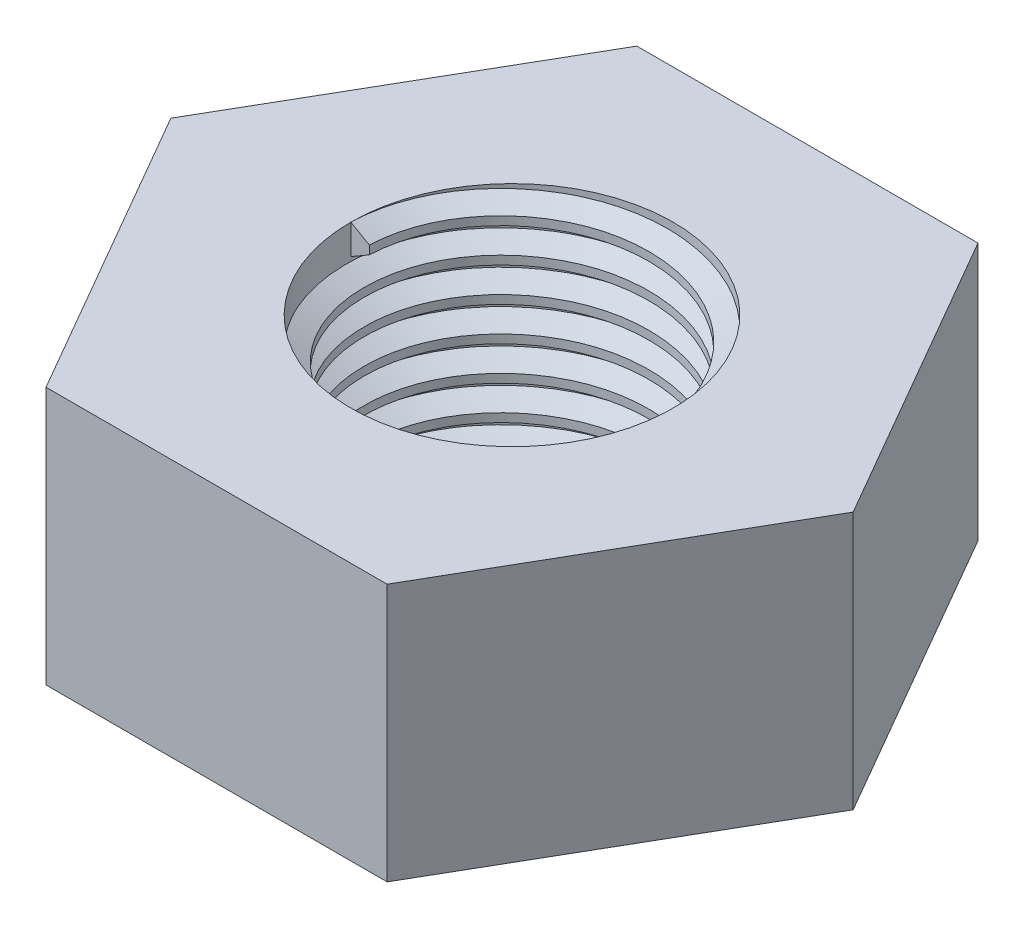
SolidWorks part; units mm, degrees
ref_plane "Ebene vorne" through (0, 0, 0) normal (0, 0, 1) x (1, 0, 0)
ref_plane "Ebene oben" through (0, 0, 0) normal (0, 1, 0) x (1, 0, 0)
ref_plane "Ebene rechts" through (0, 0, 0) normal (1, 0, 0) x (0, 0, -1)
sketch "Skizze2" plane through (0, 0, 0) normal (0, 1, 0) x (1, 0, 0)
  line L1 (3.1754, 0) -> (1.5877, 2.75)
  line L2 (1.5877, 2.75) -> (-1.5877, 2.75)
  line L3 (-1.5877, 2.75) -> (-3.1754, 0)
  line L4 (-3.1754, 0) -> (-1.5877, -2.75)
  line L5 (-1.5877, -2.75) -> (1.5877, -2.75)
  line L6 (1.5877, -2.75) -> (3.1754, 0)
  circle A0 centre (0, 0) radius 2.75 construction
  point P1 (0, 0)
  dimension "D1" = 5.5
extrude "Aufsatz-Linear austragen1" add sketch "Skizze2" along normal blind 2.4
sketch "Skizze3" plane through (0, 2.4, 0) normal (0, 1, 0) x (1, 0, 0)
  circle A0 centre (0, 0) radius 1.5
  dimension "D1" = 3
extrude "Schnitt-Linear austragen1" cut sketch "Skizze3" against normal up to surface (2.4 mm away) up to face at (0, 0, 0)
thread "Gewinde1" pitch 0.3175 method extrude profile "Gewindeprofil1" start angle 0, offset 0, length 0, pitch 0.3175, diameter 3
ref_plane "Ebene4" through (-1.5, 2.4, 0) normal (0, 0, 1) x (-1, 0, 0)
sketch "Gewindeprofil1" plane through (-1.5, 2.4, 0) normal (0, 0, 1) x (-1, 0, 0)
  line L0 (0, 0) -> (0, 0.3175) construction
  line L11 (0, 0) -> (0, 0.2778)
  line L12 (0, 0.2778) -> (-0.1719, 0.1786)
  line L13 (-0.1719, 0.1786) -> (-0.1719, 0.0992)
  line L15 (-0.1719, 0.0992) -> (0, 0)
  line L17 (-0.1719, 0.1389) -> (0, 0.1389) construction
  point P2 (0, 0)
  dimension "Pitch" = 0.3175
  dimension "Profile_Angle" = 60
  dimension "Profile_Land" = 0.0794
  dimension "Profile_Height" = 0.1719
